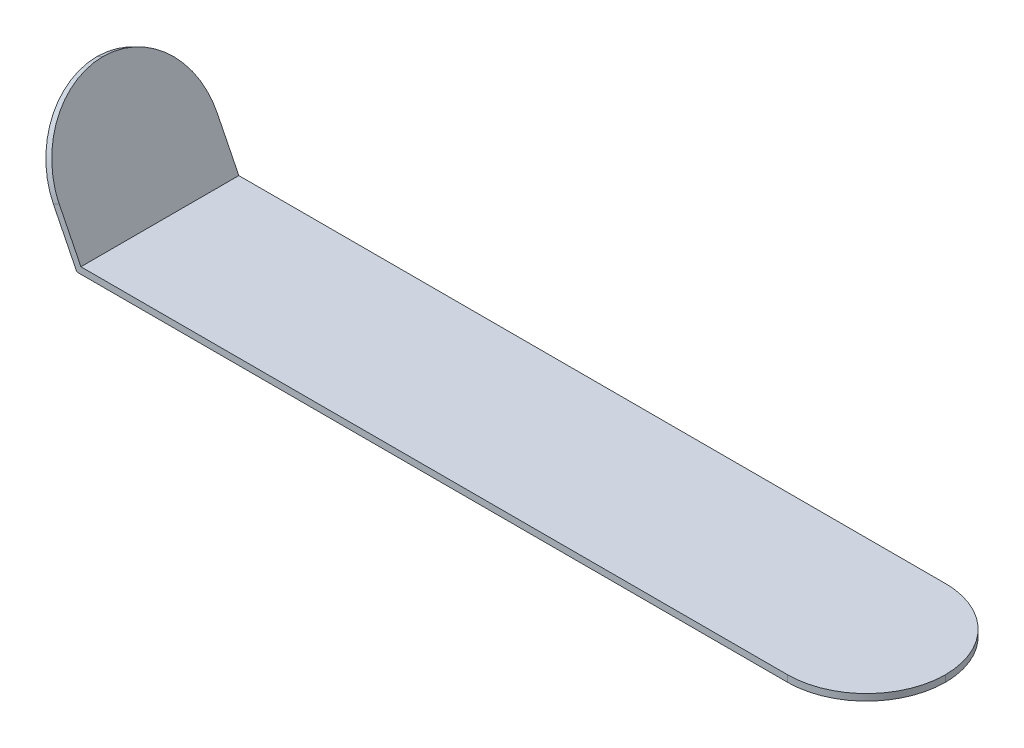
SolidWorks part; units mm, degrees
ref_plane "Plano frontal" through (0, 0, 0) normal (0, 0, 1) x (1, 0, 0)
ref_plane "Plano superior" through (0, 0, 0) normal (0, 1, 0) x (1, 0, 0)
ref_plane "Plano direito" through (0, 0, 0) normal (1, 0, 0) x (0, 0, -1)
sketch "Esboço1" plane through (0, 0, 0) normal (0, 0, 1) x (1, 0, 0)
  line L0 (0, 0) -> (60, 0)
  line L1 (60, 0) -> (60, 0.5)
  line L2 (60, 0.5) -> (0.3094, 0.5)
  line L3 (0.3094, 0.5) -> (-4.0145, 9.1724)
  line L4 (-4.0145, 9.1724) -> (-4.462, 8.9493)
  line L5 (-4.462, 8.9493) -> (0, 0)
  dimension "D1" = 60
  dimension "D2" = 10
  dimension "D3" = 116.5
  dimension "D4" = 0.5
  dimension "D5" = 0.5
extrude "Ressalto-extrusão1" add sketch "Esboço1" along normal blind 12
fillet "Filete1" radius 6 4 edges at (60, 0.25, 12) (60, 0.25, 0) (-4.2382, 9.0609, 12) (-4.2382, 9.0609, 0) first distance on face at (18.6388, 3.187, 12) first distance on face at (18.6388, 3.187, 0)
